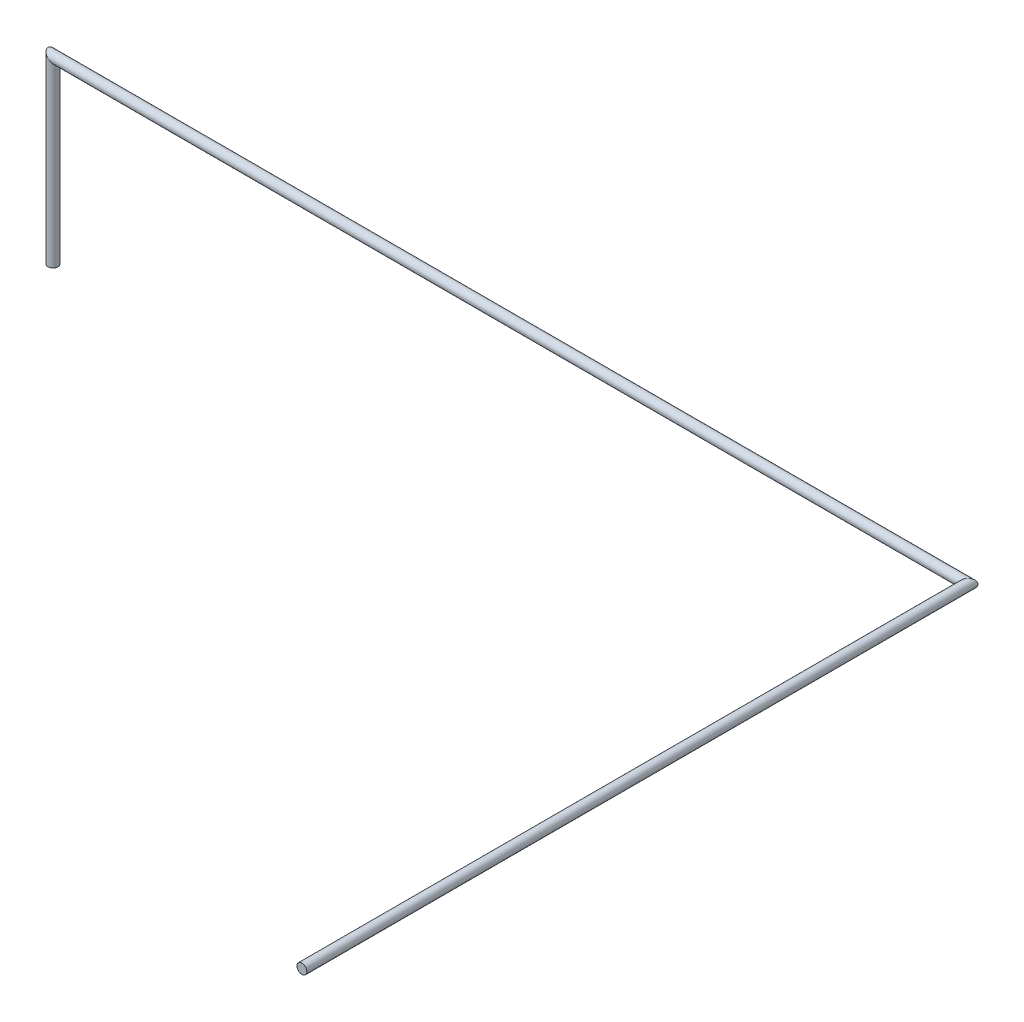
SolidWorks part; units mm, degrees
ref_plane "Alzado" through (0, 0, 0) normal (0, 0, 1) x (1, 0, 0)
ref_plane "Planta" through (0, 0, 0) normal (0, 1, 0) x (1, 0, 0)
ref_plane "Vista lateral" through (0, 0, 0) normal (1, 0, 0) x (0, 0, -1)
sketch "Croquis1" plane through (0, 0, 0) normal (0, 1, 0) x (1, 0, 0)
  circle A0 centre (0, 0) radius 12.7
  dimension "D1" = 25.4
extrude "Saliente-Extruir1" add sketch "Croquis1" along normal blind 10
sketch3d "Croquis3D1"
  line L0 (0, 10, 0) -> (0, 460, 0)
  line L1 (0, 10, 0) -> (0, 0, 0) construction
  line L2 (0, 460, 0) -> (2335, 460, 0)
  line L3 (2335, 460, 0) -> (2335, 460, 1700)
  dimension "D1" = 450
  dimension "D2" = 2335
  dimension "D3" = 1700
sketch "Croquis2" plane through (0, 10, 0) normal (0, 1, 0) x (1, 0, 0)
  circle A0 centre (0, 0) radius 12.7
sweep "Barrer1" add profiles "Croquis2" path "Croquis3D1"
sketch "Croquis3" plane through (0, 0, 0) normal (0, -1, 0) x (1, 0, 0)
  line L1 (-12.2852, -0.5796) -> (-13.1148, -0.5796)
  line L2 (-12.2852, -0.5796) -> (-12.2852, 0.5796)
  line L3 (-12.2852, 0.5796) -> (-13.1148, 0.5796)
  line L4 (-13.1148, -0.5796) -> (-13.1148, 0.5796)
  line L5 (-12.2852, -0.5796) -> (-13.1148, 0.5796) construction
  line L6 (-12.2852, 0.5796) -> (-13.1148, -0.5796) construction
  circle A0 centre (0, 0) radius 12.7 construction
  point P0 (-12.7, 0)
extrude "Saliente-Extruir2" add sketch "Croquis3" against normal blind 3
